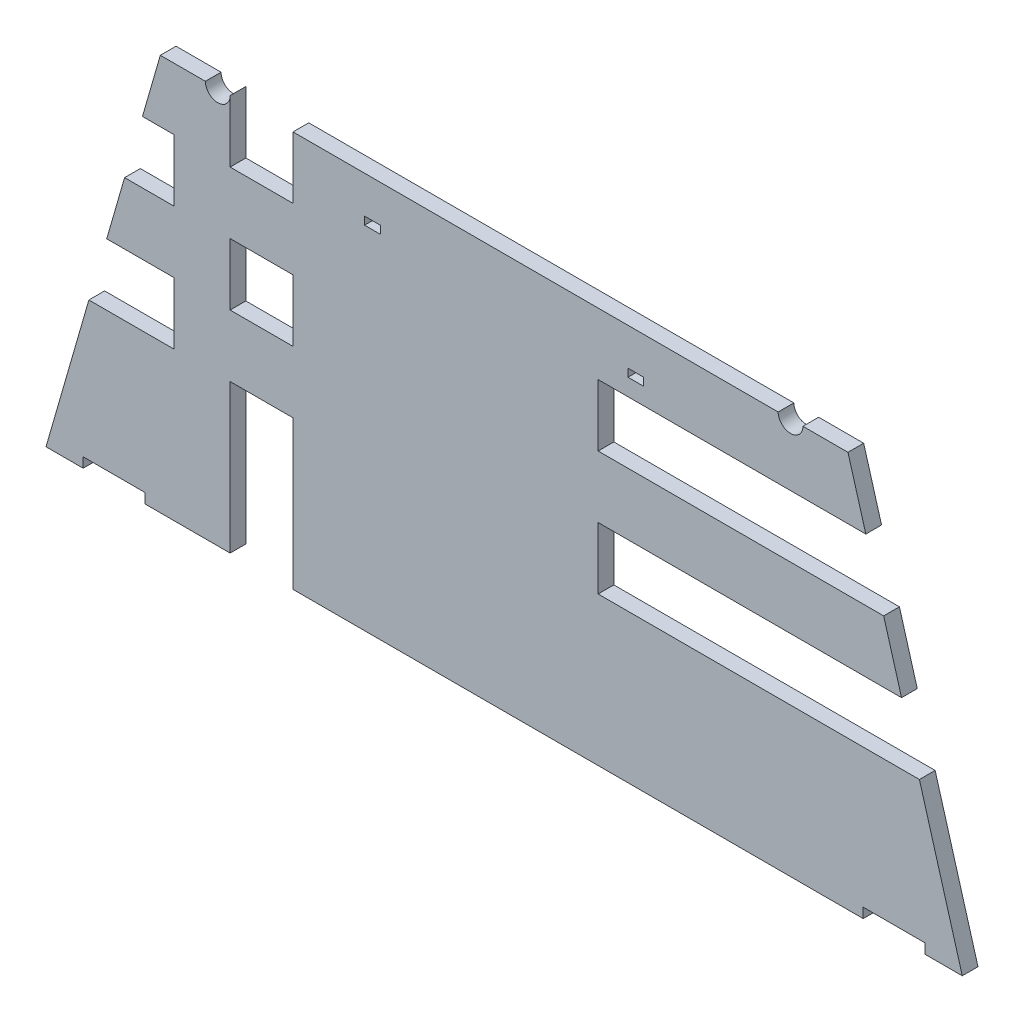
SolidWorks part; units mm, degrees
ref_plane "Front Plane" through (0, 0, 0) normal (0, 0, 1) x (1, 0, 0)
ref_plane "Top Plane" through (0, 0, 0) normal (0, 1, 0) x (1, 0, 0)
ref_plane "Right Plane" through (0, 0, 0) normal (1, 0, 0) x (0, 0, -1)
sketch "Sketch1" plane through (0, 0, 0) normal (0, 0, 1) x (1, 0, 0)
  line L0 (-145, 0) -> (-145, 4)
  line L1 (145, 0) -> (-85.25, 0)
  line L2 (-145, 4) -> (-170, 4)
  line L3 (-170, 4) -> (-170, 0)
  line L4 (-170, 0) -> (-185, 0)
  line L5 (-185, 0) -> (-167.6889, 60)
  line L6 (-167.6889, 60) -> (-133.35, 60)
  line L7 (-133.35, 85) -> (-133.35, 60)
  line L8 (37.95, 60) -> (37.95, 0) construction
  line L12 (-133.35, 85) -> (-160.4759, 85)
  line L13 (-160.4759, 85) -> (-153.263, 110)
  line L14 (-153.263, 110) -> (-133.35, 110)
  line L15 (-133.35, 110) -> (-133.35, 135)
  line L16 (-133.35, 135) -> (-146.05, 135)
  line L17 (-146.05, 135) -> (-138.837, 160)
  line L18 (-138.837, 160) -> (-120.65, 160)
  line L19 (-133.35, 135) -> (-133.35, 160) construction
  line L20 (-110.65, 160) -> (-110.65, 135)
  line L21 (-110.65, 135) -> (-85.25, 135)
  line L22 (-85.25, 135) -> (-85.25, 160)
  line L23 (-85.25, 160) -> (0, 160)
  line L24 (-50, 145) -> (-50, 141.825)
  line L25 (-50, 141.825) -> (-56.35, 141.825)
  line L26 (-56.35, 141.825) -> (-56.35, 145)
  line L27 (-56.35, 145) -> (-50, 145)
  line L28 (-133.35, 110) -> (-133.35, 85) construction
  line L30 (-133.35, 60) -> (-133.35, 0) construction
  line L31 (0, 160) -> (0, 0) construction
  line L32 (-110.65, 110) -> (-110.65, 85)
  line L34 (37.95, 110) -> (37.95, 85) construction
  line L35 (37.95, 135) -> (37.95, 160) construction
  line L36 (56.35, 145) -> (50, 145)
  line L37 (56.35, 141.825) -> (56.35, 145)
  line L38 (50, 141.825) -> (56.35, 141.825)
  line L39 (50, 145) -> (50, 141.825)
  line L40 (0, 160) -> (110.65, 160)
  line L41 (-110.65, 85) -> (-85.25, 85)
  line L42 (-85.25, 85) -> (-85.25, 110)
  line L43 (138.837, 160) -> (120.65, 160)
  line L44 (146.05, 135) -> (138.837, 160)
  line L45 (37.95, 135) -> (146.05, 135)
  line L46 (37.95, 110) -> (37.95, 135)
  line L47 (153.263, 110) -> (37.95, 110)
  line L48 (160.4759, 85) -> (153.263, 110)
  line L49 (37.95, 85) -> (160.4759, 85)
  line L50 (37.95, 60) -> (37.95, 85)
  line L55 (167.6889, 60) -> (37.95, 60)
  line L56 (185, 0) -> (167.6889, 60)
  line L57 (170, 0) -> (185, 0)
  line L58 (170, 4) -> (170, 0)
  line L59 (145, 4) -> (170, 4)
  line L60 (145, 0) -> (145, 4)
  line L61 (-85.25, 110) -> (-110.65, 110)
  line L66 (-110.65, 60) -> (-110.65, 0)
  line L67 (-110.65, 60) -> (-85.25, 60)
  line L68 (-85.25, 60) -> (-85.25, 0)
  line L69 (-110.65, 0) -> (-145, 0)
  arc A0 (-110.65, 160) -> (-120.65, 160) centre (-115.65, 160) cw
  arc A1 (110.65, 160) -> (120.65, 160) centre (115.65, 160) ccw
  dimension "D7" = 6.35
  dimension "D2" = 5
  dimension "D1" = 25.4
  dimension "D3" = 4
  dimension "D4" = 25
  dimension "D5" = 160
  dimension "D6" = 15
  dimension "D8" = 3.175
  dimension "D9" = 15
  dimension "D10" = 50
  dimension "D11" = 12.7
  dimension "D12" = 12.7
  dimension "D13" = 145
  dimension "D14" = 120.65
  dimension "D15" = 72.7
  dimension "D16" = 60
extrude "Extrude1" add sketch "Sketch1" along normal blind 6.35
